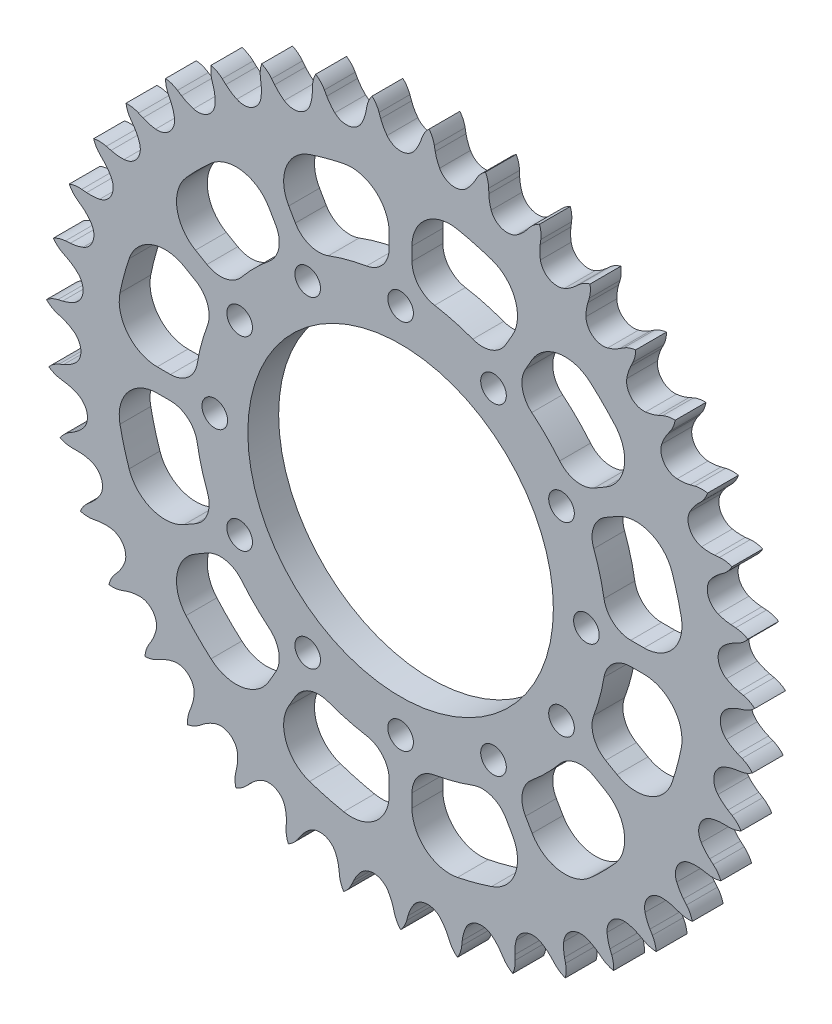
SolidWorks part; units mm, degrees
note: '?' marks a value the reader was unsure of.
material "7075-T6 (SN)"
ref_plane "Front Plane" through (0, 0, 0) normal (0, 0, 1) x (1, 0, 0)
ref_plane "Top Plane" through (0, 0, 0) normal (0, 1, 0) x (1, 0, 0)
ref_plane "Right Plane" through (0, 0, 0) normal (1, 0, 0) x (0, 0, -1)
sketch "Work Sketch" plane through (0, 0, 0) normal (0, 0, 1) x (1, 0, 0)
  line L0 (0, 0) -> (0, 160.4542) construction
  line L1 (-112.0919, 78.9148) -> (87.2579, 78.9148) construction
  line L2 (5.102, 120.8822) -> (5.102, 112.9699) construction
  line L3 (-12.8497, 82.6953) -> (16.7256, 82.6953) construction
  line L4 (5.102, 82.6953) -> (-6.0879, 74.4036) construction
  line L5 (5.102, 82.6953) -> (-4.6505, 79.1506) construction
  line L6 (-4.6505, 79.1506) -> (-6.8863, 85.3019)
  line L7 (-11.5114, 78.0206) -> (-7.1525, 78.0206) construction
  line L8 (-11.0765, 124.7602) -> (-11.0765, 110.2345) construction
  line L9 (0, 0) -> (-3.4402, 42.6146) construction
  circle A0 centre (0, 0) radius 78.9148
  circle A1 centre (0, 78.9148) radius 4.0088
  arc A2 (-4.6505, 79.1506) -> (-3.2209, 76.5281) centre (5.0804, 82.7541) ccw
  circle A3 centre (-11.0765, 78.0206) radius 6.4254
  point P23 (-3.2209, 76.5281)
  dimension "D1" = 157.8295
  dimension "D8" = 10.3767
  dimension "D2" = 8.0177
  dimension "D3" = 5.102
  dimension "D4" = 3.7806
  dimension "D5" = 36.538
  dimension "D6" = 16.564
  dimension "D7" = 10.3767
  dimension "D9" = 0.8942
  dimension "D10" = 11.0765
  dimension "D11" = 4.615
sketch "Teeth Sketch" plane through (0, 0, 0) normal (0, 0, 1) x (1, 0, 0)
  line L0 (5.0376, 80.2155) -> (4.6505, 79.1506)
  line L1 (-7.4865, 92.7372) -> (-4.7839, 59.2593) construction
  line L2 (0, 0) -> (-10.9133, 132.3061) construction
  line L3 (7.8951, 79.9848) -> (8.1063, 78.8717)
  line L4 (16093.3137, -199351.4616) -> (-16096.7539, 199394.0762) construction
  line L5 (0, 146.3285) -> (0, 56.9858) construction
  line L6 (17.8398, 78.3686) -> (17.287, 77.3797)
  line L7 (0, -200000) -> (0, 200160.4542) construction
  line L8 (20.6234, 77.6826) -> (20.6533, 76.5499)
  line L9 (-4.6505, 79.1506) -> (-6.8863, 85.3019) construction
  line L10 (44.1616, 67.154) -> (43.8313, 66.0702)
  line L11 (-5.0376, 80.2155) -> (-4.6505, 79.1506)
  line L12 (30.18, 74.4921) -> (29.4757, 73.6046)
  line L13 (32.8175, 73.3684) -> (32.6653, 72.2456)
  line L14 (41.7385, 68.6862) -> (40.901, 67.9232)
  line L15 (52.2161, 61.1014) -> (51.267, 60.4826)
  line L16 (54.362, 59.2003) -> (53.8621, 58.1836)
  line L17 (61.3413, 51.9341) -> (60.3052, 51.4756)
  line L18 (63.1544, 49.7134) -> (62.4979, 48.79)
  line L19 (68.8777, 41.4218) -> (67.7815, 41.1354)
  line L20 (70.3112, 38.939) -> (69.515, 38.1328)
  line L21 (74.6303, 29.8366) -> (73.5023, 29.7298)
  line L22 (75.6469, 27.156) -> (74.7318, 26.488)
  line L23 (78.45, 17.4787) -> (77.3195, 17.5542)
  line L24 (79.0234, 14.6698) -> (78.013, 14.1572)
  line L25 (80.2378, 4.6681) -> (79.1341, 4.9239)
  line L26 (80.3533, 1.8035) -> (79.2737, 1.4597)
  line L27 (79.9476, -8.2634) -> (78.8992, -7.8338)
  line L28 (79.602, -11.1094) -> (78.4813, -11.2756)
  line L29 (77.5867, -20.9809) -> (76.6208, -20.3887)
  line L30 (76.7891, -23.7346) -> (75.6562, -23.7189)
  line L31 (73.2164, -33.155) -> (72.358, -32.4155)
  line L32 (71.9874, -35.7451) -> (70.8717, -35.5478)
  line L33 (66.9499, -44.4704) -> (66.2212, -43.6028)
  line L34 (65.3213, -46.8298) -> (64.2517, -46.4561)
  line L35 (58.9493, -54.634) -> (58.3693, -53.6608)
  line L36 (56.9634, -56.7016) -> (55.9676, -56.1612)
  line L37 (49.422, -63.3827) -> (49.0056, -62.329)
  line L38 (47.1301, -65.1049) -> (46.2339, -64.4118)
  line L39 (38.6147, -70.4897) -> (38.3727, -69.3829)
  line L40 (36.0763, -71.822) -> (35.3028, -70.9941)
  line L41 (26.8073, -75.7712) -> (26.746, -74.6398)
  line L42 (24.088, -76.679) -> (23.4574, -75.7377)
  line L43 (14.3056, -79.0901) -> (14.4266, -77.9636)
  line L44 (11.4759, -79.55) -> (11.0044, -78.5198)
  line L45 (1.4334, -80.3607) -> (1.7335, -79.2682)
  line L46 (-1.4334, -80.3607) -> (-1.7335, -79.2682)
  line L47 (-11.4759, -79.55) -> (-11.0044, -78.5198)
  line L48 (-14.3056, -79.0901) -> (-14.4266, -77.9636)
  line L49 (-24.088, -76.679) -> (-23.4574, -75.7377)
  line L50 (-26.8073, -75.7712) -> (-26.746, -74.6398)
  line L51 (-36.0763, -71.822) -> (-35.3028, -70.9941)
  line L52 (-38.6147, -70.4897) -> (-38.3727, -69.3829)
  line L53 (-47.1301, -65.1049) -> (-46.2339, -64.4118)
  line L54 (-49.422, -63.3827) -> (-49.0056, -62.329)
  line L55 (-56.9634, -56.7016) -> (-55.9676, -56.1612)
  line L56 (-58.9493, -54.634) -> (-58.3693, -53.6608)
  line L57 (-65.3213, -46.8298) -> (-64.2517, -46.4561)
  line L58 (-66.9499, -44.4704) -> (-66.2212, -43.6028)
  line L59 (-71.9874, -35.7451) -> (-70.8717, -35.5478)
  line L60 (-73.2164, -33.155) -> (-72.358, -32.4155)
  line L61 (-76.7891, -23.7346) -> (-75.6562, -23.7189)
  line L62 (-77.5867, -20.9809) -> (-76.6208, -20.3887)
  line L63 (-79.602, -11.1094) -> (-78.4813, -11.2756)
  line L64 (-79.9476, -8.2634) -> (-78.8992, -7.8338)
  line L65 (-80.3533, 1.8035) -> (-79.2737, 1.4597)
  line L66 (-80.2378, 4.6681) -> (-79.1341, 4.9239)
  line L67 (-79.0234, 14.6698) -> (-78.013, 14.1572)
  line L68 (-78.45, 17.4787) -> (-77.3195, 17.5542)
  line L69 (-75.6469, 27.156) -> (-74.7318, 26.488)
  line L70 (-74.6303, 29.8366) -> (-73.5023, 29.7298)
  line L71 (-70.3112, 38.939) -> (-69.515, 38.1328)
  line L72 (-68.8777, 41.4218) -> (-67.7815, 41.1354)
  line L73 (-63.1544, 49.7134) -> (-62.4979, 48.79)
  line L74 (-61.3413, 51.9341) -> (-60.3052, 51.4756)
  line L75 (-54.362, 59.2003) -> (-53.8621, 58.1836)
  line L76 (-52.2161, 61.1014) -> (-51.267, 60.4826)
  line L77 (-44.1616, 67.154) -> (-43.8313, 66.0702)
  line L78 (-41.7385, 68.6862) -> (-40.901, 67.9232)
  line L79 (-32.8175, 73.3684) -> (-32.6653, 72.2456)
  line L80 (-30.18, 74.4921) -> (-29.4757, 73.6046)
  line L81 (-20.6234, 77.6826) -> (-20.6533, 76.5499)
  line L82 (-17.8398, 78.3686) -> (-17.287, 77.3797)
  line L83 (-7.8951, 79.9848) -> (-8.1063, 78.8717)
  arc A0 (-6.8336, 82.8459) -> (-5.0376, 80.2155) centre (-11.0765, 78.0206) cw
  circle A1 centre (-11.0765, 78.0206) radius 6.4254 construction
  arc A2 (-3.1753, 76.4677) -> (-4.6505, 79.1506) centre (5.0804, 82.7541) cw
  arc A3 (-4.6505, 79.1506) -> (-3.2209, 76.5281) centre (5.0804, 82.7541) ccw construction
  circle A4 centre (0, 78.9148) radius 4.0088 construction
  arc A5 (-3.1753, 76.4677) -> (3.1753, 76.4677) centre (0, 78.9148) ccw
  arc A6 (3.1753, 76.4677) -> (4.6505, 79.1506) centre (-5.0804, 82.7541) ccw
  arc A7 (6.8336, 82.8459) -> (5.0376, 80.2155) centre (11.0765, 78.0206) ccw
  arc A8 (6.5443, 82.8692) -> (7.8951, 79.9848) centre (1.5824, 78.787) cw
  arc A9 (9.1321, 75.9868) -> (8.1063, 78.8717) centre (18.2893, 80.8676) cw
  arc A10 (9.1321, 75.9868) -> (15.4004, 74.9681) centre (12.6588, 77.8928) ccw
  arc A11 (15.4004, 74.9681) -> (17.287, 77.3797) centre (8.2601, 82.4975) ccw
  arc A12 (20.0345, 80.6769) -> (17.8398, 78.3686) centre (23.4484, 75.2334) ccw
  arc A13 (19.7528, 80.7463) -> (20.6234, 77.6826) centre (14.2002, 77.5129) cw
  arc A14 (21.203, 73.5379) -> (20.6533, 76.5499) centre (31.0245, 76.8865) cw
  arc A15 (21.203, 73.5379) -> (27.2267, 71.5268) centre (24.9898, 74.8535) ccw
  arc A16 (27.2267, 71.5268) -> (29.4757, 73.6046) centre (21.3867, 80.1041) ccw
  arc A17 (32.7165, 76.4184) -> (30.18, 74.4921) centre (35.2131, 70.4978) ccw
  arc A18 (32.4496, 76.5321) -> (32.8175, 73.3684) centre (26.4502, 74.2313) cw
  arc A19 (32.7247, 69.1844) -> (32.6653, 72.2456) centre (42.9562, 70.9142) cw
  arc A20 (32.7247, 69.1844) -> (38.3479, 66.2331) centre (36.6735, 69.8756) ccw
  arc A21 (38.3479, 66.2331) -> (40.901, 67.9232) centre (33.9593, 75.6361) ccw
  arc A22 (44.5512, 70.1807) -> (41.7385, 68.6862) centre (46.0657, 63.9363) ccw
  arc A23 (44.306, 70.3358) -> (44.1616, 67.154) centre (38.0153, 69.0271) cw
  arc A24 (43.3989, 63.039) -> (43.8313, 66.0702) centre (53.7754, 63.1052) cw
  arc A25 (43.3989, 63.039) -> (48.4758, 59.224) centre (47.4074, 63.0878) ccw
  arc A26 (48.4758, 59.224) -> (51.267, 60.4826) centre (45.6524, 69.2092) ccw
  arc A27 (55.2321, 62.1253) -> (52.2161, 61.1014) centre (55.7253, 55.7189) ccw
  arc A28 (55.0149, 62.3178) -> (54.362, 59.2003) centre (48.5957, 62.0351) cw
  arc A29 (52.9491, 55.261) -> (53.8621, 58.1836) centre (63.2018, 53.6618) cw
  arc A30 (52.9491, 55.261) -> (57.3483, 50.681) centre (56.9135, 54.6662) ccw
  arc A31 (57.3483, 50.681) -> (60.3052, 51.4756) centre (56.1632, 60.9898) ccw
  arc A32 (64.4824, 52.461) -> (61.3413, 51.9341) centre (63.9416, 46.0584) ccw
  arc A33 (64.2989, 52.6858) -> (63.1544, 49.7134) centre (57.9175, 53.4365) cw
  arc A34 (61.1279, 46.0518) -> (62.4979, 48.79) centre (70.9913, 42.8287) cw
  arc A35 (61.1279, 46.0518) -> (64.7354, 40.8254) centre (64.9456, 44.8287) ccw
  arc A36 (64.7354, 40.8254) -> (67.7815, 41.1354) centre (65.2193, 51.1908) ccw
  arc A37 (72.0627, 41.4379) -> (68.8777, 41.4218) centre (70.5018, 35.205) ccw
  arc A38 (71.9177, 41.6892) -> (70.3112, 38.939) centre (65.7393, 43.4539) cw
  arc A39 (67.7235, 35.6498) -> (69.515, 38.1328) centre (76.9422, 30.8862) cw
  arc A40 (67.7235, 35.6498) -> (70.446, 29.9124) centre (71.2956, 33.8302) ccw
  arc A41 (70.446, 29.9124) -> (73.5023, 29.7298) centre (72.5864, 40.0659) ccw
  arc A42 (77.7767, 29.3416) -> (74.6303, 29.8366) centre (75.2361, 23.4398) ccw
  arc A43 (77.6738, 29.6129) -> (75.6469, 27.156) centre (71.8585, 32.3458) cw
  arc A44 (72.5652, 24.3246) -> (74.7318, 26.488) centre (80.9003, 18.1439) cw
  arc A45 (72.5652, 24.3246) -> (74.332, 18.2247) centre (75.7991, 21.9555) ccw
  arc A46 (74.332, 18.2247) -> (77.3195, 17.5542) centre (78.0734, 27.9034) ccw
  arc A47 (81.4762, 16.4854) -> (78.45, 17.4787) centre (78.0218, 11.0675) ccw
  arc A48 (81.4182, 16.7697) -> (79.0234, 14.6698) centre (76.1166, 20.4) cw
  arc A49 (75.5274, 12.3693) -> (78.013, 14.1572) centre (82.7631, 4.9316) cw
  arc A50 (75.5274, 12.3693) -> (76.2929, 6.065) centre (78.3394, 9.5121) ccw
  arc A51 (76.2929, 6.065) -> (79.1341, 4.9239) centre (81.5384, 15.0182) ccw
  arc A52 (83.0656, 3.2022) -> (80.2378, 4.6681) centre (78.7868, -1.5914) ccw
  arc A53 (83.0539, 3.4922) -> (80.3533, 1.8035) centre (78.4033, 7.9259) cw
  arc A54 (76.5335, 0.0937) -> (79.2737, 1.4597) centre (82.4825, -8.4084) cw
  arc A55 (76.5335, 0.0937) -> (76.2778, -6.2518) centre (78.8508, -3.1776) ccw
  arc A56 (76.2778, -6.2518) -> (78.8992, -7.8338) centre (82.8916, 1.7441) ccw
  arc A57 (82.5035, -10.1639) -> (79.9476, -8.2634) centre (77.5113, -14.2091) ccw
  arc A58 (82.5385, -9.8758) -> (79.602, -11.1094) centre (78.6594, -4.7535) cw
  arc A59 (75.5574, -12.1844) -> (78.4813, -11.2756) centre (80.0655, -21.5307) cw
  arc A60 (75.5574, -12.1844) -> (74.2872, -18.4066) centre (77.3199, -15.785) ccw
  arc A61 (74.2872, -18.4066) -> (76.6208, -20.3887) centre (82.0979, -11.5753) ccw
  arc A62 (79.8047, -23.2668) -> (77.5867, -20.9809) centre (74.2283, -26.4587) ccw
  arc A63 (79.8855, -22.9881) -> (76.7891, -23.7346) centre (76.8783, -17.3098) cw
  arc A64 (72.6245, -24.1469) -> (75.6562, -23.7189) centre (75.5749, -34.0953) cw
  arc A65 (72.6245, -24.1469) -> (70.3725, -30.0848) centre (73.7866, -27.9836) ccw
  arc A66 (70.3725, -30.0848) -> (72.358, -32.4155) centre (79.178, -24.5948) ccw
  arc A67 (75.039, -35.7671) -> (73.2164, -33.155) centre (69.0227, -38.0232) ccw
  arc A68 (75.1634, -35.5049) -> (71.9874, -35.7451) centre (73.106, -29.4178) cw
  arc A69 (67.8106, -35.484) -> (70.8717, -35.5478) centre (69.127, -45.7768) cw
  arc A70 (67.8106, -35.484) -> (64.6353, -40.9837) centre (68.3422, -39.4574) ccw
  arc A71 (64.6353, -40.9837) -> (66.2212, -43.6028) centre (74.2074, -36.9773) ccw
  arc A72 (68.3299, -47.341) -> (66.9499, -44.4704) centre (62.0296, -48.6028) ccw
  arc A73 (68.4947, -47.1022) -> (65.3213, -46.8298) centre (67.4404, -40.7639) cw
  arc A74 (61.2404, -45.902) -> (64.2517, -46.4561) centre (60.8887, -56.2728) cw
  arc A75 (61.2404, -45.902) -> (57.224, -50.8212) centre (61.1278, -49.9093) ccw
  arc A76 (57.224, -50.8212) -> (58.3693, -53.6608) centre (67.3148, -48.4022) ccw
  arc A77 (59.851, -57.6888) -> (58.9493, -54.634) centre (53.4299, -57.9236) ccw
  arc A78 (60.052, -57.4796) -> (56.9634, -56.7016) centre (60.0281, -51.0542) cw
  arc A79 (53.0842, -55.1313) -> (55.9676, -56.1612) centre (51.0734, -65.3113) cw
  arc A80 (53.0842, -55.1313) -> (48.3307, -59.3425) centre (52.3302, -59.0685) ccw
  arc A81 (48.3307, -59.3425) -> (49.0056, -62.329) centre (58.6789, -58.5735) ccw
  arc A82 (49.822, -66.5425) -> (49.422, -63.3827) centre (43.4464, -65.7443) ccw
  arc A83 (50.054, -66.3682) -> (47.1301, -65.1049) centre (51.0611, -60.0222) cw
  arc A84 (43.5531, -62.9326) -> (46.2339, -64.4118) centre (39.9354, -72.6583) cw
  arc A85 (43.5531, -62.9326) -> (38.1856, -66.3268) centre (42.1772, -66.698) ccw
  arc A86 (38.1856, -66.3268) -> (38.3727, -69.3829) centre (48.5231, -67.2277) ccw
  arc A87 (38.5026, -73.6728) -> (38.6147, -70.4897) centre (32.3376, -71.8622) ccw
  arc A88 (38.7596, -73.538) -> (36.0763, -71.822) centre (40.7716, -67.4357) cw
  arc A89 (32.894, -69.1041) -> (35.3028, -70.9941) centre (27.763, -78.1234) cw
  arc A90 (32.894, -69.1041) -> (27.0516, -71.5933) centre (30.932, -72.6) ccw
  arc A91 (27.0516, -71.5933) -> (26.746, -74.6398) centre (37.1107, -74.1408) ccw
  arc A92 (26.1861, -78.8951) -> (26.8073, -75.7712) centre (20.3913, -76.1189) ccw
  arc A93 (26.4613, -78.8032) -> (24.088, -76.679) centre (29.4261, -73.1027) cw
  arc A94 (21.3829, -73.4858) -> (23.4574, -75.7377) centre (14.8716, -81.5653) cw
  arc A95 (21.3829, -73.4858) -> (15.2169, -75.0055) centre (18.8855, -76.6216) ccw
  arc A96 (15.2169, -75.0055) -> (14.4266, -77.9636) centre (24.7371, -79.1336) ccw
  arc A97 (13.1913, -82.0739) -> (14.3056, -79.0901) centre (7.9169, -78.4042) ccw
  arc A98 (13.4777, -82.0274) -> (11.4759, -79.55) centre (17.3186, -76.8763) cw
  arc A99 (9.3181, -75.9642) -> (11.0044, -78.5198) centre (1.595, -82.8946) cw
  arc A100 (9.3181, -75.9642) -> (2.9881, -76.4752) centre (6.35, -78.6589) ccw
  arc A101 (2.9881, -76.4752) -> (1.7335, -79.2682) centre (11.7228, -82.077) ccw
  arc A102 (-0.1451, -83.1271) -> (1.4334, -80.3607) centre (-4.7625, -78.6589) ccw
  arc A103 (0.1451, -83.1271) -> (-1.4334, -80.3607) centre (4.7625, -78.6589) cw
  arc A104 (-2.9881, -76.4752) -> (-1.7335, -79.2682) centre (-11.7228, -82.077) cw
  arc A105 (-2.9881, -76.4752) -> (-9.3181, -75.9642) centre (-6.35, -78.6589) ccw
  arc A106 (-9.3181, -75.9642) -> (-11.0044, -78.5198) centre (-1.595, -82.8946) ccw
  arc A107 (-13.4777, -82.0274) -> (-11.4759, -79.55) centre (-17.3186, -76.8763) ccw
  arc A108 (-13.1913, -82.0739) -> (-14.3056, -79.0901) centre (-7.9169, -78.4042) cw
  arc A109 (-15.2169, -75.0055) -> (-14.4266, -77.9636) centre (-24.7371, -79.1336) cw
  arc A110 (-15.2169, -75.0055) -> (-21.3829, -73.4858) centre (-18.8855, -76.6216) ccw
  arc A111 (-21.3829, -73.4858) -> (-23.4574, -75.7377) centre (-14.8716, -81.5653) ccw
  arc A112 (-26.4613, -78.8032) -> (-24.088, -76.679) centre (-29.4261, -73.1027) ccw
  arc A113 (-26.1861, -78.8951) -> (-26.8073, -75.7712) centre (-20.3913, -76.1189) cw
  arc A114 (-27.0516, -71.5933) -> (-26.746, -74.6398) centre (-37.1107, -74.1408) cw
  arc A115 (-27.0516, -71.5933) -> (-32.894, -69.1041) centre (-30.932, -72.6) ccw
  arc A116 (-32.894, -69.1041) -> (-35.3028, -70.9941) centre (-27.763, -78.1234) ccw
  arc A117 (-38.7596, -73.538) -> (-36.0763, -71.822) centre (-40.7716, -67.4357) ccw
  arc A118 (-38.5026, -73.6728) -> (-38.6147, -70.4897) centre (-32.3376, -71.8622) cw
  arc A119 (-38.1856, -66.3268) -> (-38.3727, -69.3829) centre (-48.5231, -67.2277) cw
  arc A120 (-38.1856, -66.3268) -> (-43.5531, -62.9326) centre (-42.1772, -66.698) ccw
  arc A121 (-43.5531, -62.9326) -> (-46.2339, -64.4118) centre (-39.9354, -72.6583) ccw
  arc A122 (-50.054, -66.3682) -> (-47.1301, -65.1049) centre (-51.0611, -60.0222) ccw
  arc A123 (-49.822, -66.5425) -> (-49.422, -63.3827) centre (-43.4464, -65.7443) cw
  arc A124 (-48.3307, -59.3425) -> (-49.0056, -62.329) centre (-58.6789, -58.5735) cw
  arc A125 (-48.3307, -59.3425) -> (-53.0842, -55.1313) centre (-52.3302, -59.0685) ccw
  arc A126 (-53.0842, -55.1313) -> (-55.9676, -56.1612) centre (-51.0734, -65.3113) ccw
  arc A127 (-60.052, -57.4796) -> (-56.9634, -56.7016) centre (-60.0281, -51.0542) ccw
  arc A128 (-59.851, -57.6888) -> (-58.9493, -54.634) centre (-53.4299, -57.9236) cw
  arc A129 (-57.224, -50.8212) -> (-58.3693, -53.6608) centre (-67.3148, -48.4022) cw
  arc A130 (-57.224, -50.8212) -> (-61.2404, -45.902) centre (-61.1278, -49.9093) ccw
  arc A131 (-61.2404, -45.902) -> (-64.2517, -46.4561) centre (-60.8887, -56.2728) ccw
  arc A132 (-68.4947, -47.1022) -> (-65.3213, -46.8298) centre (-67.4404, -40.7639) ccw
  arc A133 (-68.3299, -47.341) -> (-66.9499, -44.4704) centre (-62.0296, -48.6028) cw
  arc A134 (-64.6353, -40.9837) -> (-66.2212, -43.6028) centre (-74.2074, -36.9773) cw
  arc A135 (-64.6353, -40.9837) -> (-67.8106, -35.484) centre (-68.3422, -39.4574) ccw
  arc A136 (-67.8106, -35.484) -> (-70.8717, -35.5478) centre (-69.127, -45.7768) ccw
  arc A137 (-75.1634, -35.5049) -> (-71.9874, -35.7451) centre (-73.106, -29.4178) ccw
  arc A138 (-75.039, -35.7671) -> (-73.2164, -33.155) centre (-69.0227, -38.0232) cw
  arc A139 (-70.3725, -30.0848) -> (-72.358, -32.4155) centre (-79.178, -24.5948) cw
  arc A140 (-70.3725, -30.0848) -> (-72.6245, -24.1469) centre (-73.7866, -27.9836) ccw
  arc A141 (-72.6245, -24.1469) -> (-75.6562, -23.7189) centre (-75.5749, -34.0953) ccw
  arc A142 (-79.8855, -22.9881) -> (-76.7891, -23.7346) centre (-76.8783, -17.3098) ccw
  arc A143 (-79.8047, -23.2668) -> (-77.5867, -20.9809) centre (-74.2283, -26.4587) cw
  arc A144 (-74.2872, -18.4066) -> (-76.6208, -20.3887) centre (-82.0979, -11.5753) cw
  arc A145 (-74.2872, -18.4066) -> (-75.5574, -12.1844) centre (-77.3199, -15.785) ccw
  arc A146 (-75.5574, -12.1844) -> (-78.4813, -11.2756) centre (-80.0655, -21.5307) ccw
  arc A147 (-82.5385, -9.8758) -> (-79.602, -11.1094) centre (-78.6594, -4.7535) ccw
  arc A148 (-82.5035, -10.1639) -> (-79.9476, -8.2634) centre (-77.5113, -14.2091) cw
  arc A149 (-76.2778, -6.2518) -> (-78.8992, -7.8338) centre (-82.8916, 1.7441) cw
  arc A150 (-76.2778, -6.2518) -> (-76.5335, 0.0937) centre (-78.8508, -3.1776) ccw
  arc A151 (-76.5335, 0.0937) -> (-79.2737, 1.4597) centre (-82.4825, -8.4084) ccw
  arc A152 (-83.0539, 3.4922) -> (-80.3533, 1.8035) centre (-78.4033, 7.9259) ccw
  arc A153 (-83.0656, 3.2022) -> (-80.2378, 4.6681) centre (-78.7868, -1.5914) cw
  arc A154 (-76.2929, 6.065) -> (-79.1341, 4.9239) centre (-81.5384, 15.0182) cw
  arc A155 (-76.2929, 6.065) -> (-75.5274, 12.3693) centre (-78.3394, 9.5121) ccw
  arc A156 (-75.5274, 12.3693) -> (-78.013, 14.1572) centre (-82.7631, 4.9316) ccw
  arc A157 (-81.4182, 16.7697) -> (-79.0234, 14.6698) centre (-76.1166, 20.4) ccw
  arc A158 (-81.4762, 16.4854) -> (-78.45, 17.4787) centre (-78.0218, 11.0675) cw
  arc A159 (-74.332, 18.2247) -> (-77.3195, 17.5542) centre (-78.0734, 27.9034) cw
  arc A160 (-74.332, 18.2247) -> (-72.5652, 24.3246) centre (-75.7991, 21.9555) ccw
  arc A161 (-72.5652, 24.3246) -> (-74.7318, 26.488) centre (-80.9003, 18.1439) ccw
  arc A162 (-77.6738, 29.6129) -> (-75.6469, 27.156) centre (-71.8585, 32.3458) ccw
  arc A163 (-77.7767, 29.3416) -> (-74.6303, 29.8366) centre (-75.2361, 23.4398) cw
  arc A164 (-70.446, 29.9124) -> (-73.5023, 29.7298) centre (-72.5864, 40.0659) cw
  arc A165 (-70.446, 29.9124) -> (-67.7235, 35.6498) centre (-71.2956, 33.8302) ccw
  arc A166 (-67.7235, 35.6498) -> (-69.515, 38.1328) centre (-76.9422, 30.8862) ccw
  arc A167 (-71.9177, 41.6892) -> (-70.3112, 38.939) centre (-65.7393, 43.4539) ccw
  arc A168 (-72.0627, 41.4379) -> (-68.8777, 41.4218) centre (-70.5018, 35.205) cw
  arc A169 (-64.7354, 40.8254) -> (-67.7815, 41.1354) centre (-65.2193, 51.1908) cw
  arc A170 (-64.7354, 40.8254) -> (-61.1279, 46.0518) centre (-64.9456, 44.8287) ccw
  arc A171 (-61.1279, 46.0518) -> (-62.4979, 48.79) centre (-70.9913, 42.8287) ccw
  arc A172 (-64.2989, 52.6858) -> (-63.1544, 49.7134) centre (-57.9175, 53.4365) ccw
  arc A173 (-64.4824, 52.461) -> (-61.3413, 51.9341) centre (-63.9416, 46.0584) cw
  arc A174 (-57.3483, 50.681) -> (-60.3052, 51.4756) centre (-56.1632, 60.9898) cw
  arc A175 (-57.3483, 50.681) -> (-52.9491, 55.261) centre (-56.9135, 54.6662) ccw
  arc A176 (-52.9491, 55.261) -> (-53.8621, 58.1836) centre (-63.2018, 53.6618) ccw
  arc A177 (-55.0149, 62.3178) -> (-54.362, 59.2003) centre (-48.5957, 62.0351) ccw
  arc A178 (-55.2321, 62.1253) -> (-52.2161, 61.1014) centre (-55.7253, 55.7189) cw
  arc A179 (-48.4758, 59.224) -> (-51.267, 60.4826) centre (-45.6524, 69.2092) cw
  arc A180 (-48.4758, 59.224) -> (-43.3989, 63.039) centre (-47.4074, 63.0878) ccw
  arc A181 (-43.3989, 63.039) -> (-43.8313, 66.0702) centre (-53.7754, 63.1052) ccw
  arc A182 (-44.306, 70.3358) -> (-44.1616, 67.154) centre (-38.0153, 69.0271) ccw
  arc A183 (-44.5512, 70.1807) -> (-41.7385, 68.6862) centre (-46.0657, 63.9363) cw
  arc A184 (-38.3479, 66.2331) -> (-40.901, 67.9232) centre (-33.9593, 75.6361) cw
  arc A185 (-38.3479, 66.2331) -> (-32.7247, 69.1844) centre (-36.6735, 69.8756) ccw
  arc A186 (-32.7247, 69.1844) -> (-32.6653, 72.2456) centre (-42.9562, 70.9142) ccw
  arc A187 (-32.4496, 76.5321) -> (-32.8175, 73.3684) centre (-26.4502, 74.2313) ccw
  arc A188 (-32.7165, 76.4184) -> (-30.18, 74.4921) centre (-35.2131, 70.4978) cw
  arc A189 (-27.2267, 71.5268) -> (-29.4757, 73.6046) centre (-21.3867, 80.1041) cw
  arc A190 (-27.2267, 71.5268) -> (-21.203, 73.5379) centre (-24.9898, 74.8535) ccw
  arc A191 (-21.203, 73.5379) -> (-20.6533, 76.5499) centre (-31.0245, 76.8865) ccw
  arc A192 (-19.7528, 80.7463) -> (-20.6234, 77.6826) centre (-14.2002, 77.5129) ccw
  arc A193 (-20.0345, 80.6769) -> (-17.8398, 78.3686) centre (-23.4484, 75.2334) cw
  arc A194 (-15.4004, 74.9681) -> (-17.287, 77.3797) centre (-8.2601, 82.4975) cw
  arc A195 (-15.4004, 74.9681) -> (-9.1321, 75.9868) centre (-12.6588, 77.8928) ccw
  arc A196 (-9.1321, 75.9868) -> (-8.1063, 78.8717) centre (-18.2893, 80.8676) ccw
  arc A197 (-6.5443, 82.8692) -> (-7.8951, 79.9848) centre (-1.5824, 78.787) ccw
  point P77 (0, 0)
  dimension "D1" = 4.615
  dimension "D2" = 4.715
  dimension "D3" = 39
extrude "Extrusion" add sketch "Teeth Sketch" along normal blind 7.2136
sketch "Sketch1" plane through (0, 0, 0) normal (0, 0, -1) x (-1, 0, 0)
  circle A0 centre (0, 0) radius 78.9443
  circle A1 centre (0, 0) radius 35.7643
  dimension "D1" = 43.18
extrude "Cut-Extrude" cut sketch "Sketch1" against normal through all both and the other way through all contours A1
ref_axis "Axis1" [suppressed] through (0, 0, 7.2136) along (0, 0, -1)?
ref_plane "Sprocket Center Plane" through (0, 0, 3.6068) normal (0, 0, 1) x (1, 0, 0)
sketch "Pitch Circle" plane through (0, 0, 3.6068) normal (0, 0, -1) x (-1, 0, 0)
  circle A0 centre (0, 0) radius 82.9531 construction
  dimension "D1" = 165.9063
sketch "Chain Pitch Circle" plane through (0, 0, 0) normal (0, 0, -1) x (-1, 0, 0)
  circle A0 centre (0, 0) radius 82.9531 construction
  dimension "D1" = 165.9063
ref_plane "Center Plane" through (0, 0, 3.6068) normal (0, 0, 1) x (1, 0, 0)
hole_wizard "Ø6.0mm Dowel Hole1" positions "Sketch7" profile "Sketch8" hole size "Ø6.0" standard "ANSI Metric" end condition through all
sketch "Sketch7" plane through (0, 0, 7.2136) normal (0, 0, 1) x (1, 0, 0)
  point P0 (-43.5, 0)
  dimension "D1" = 43.5
sketch "Sketch8" plane through (-43.5, 0, 7.2136) normal (1, 0, 0) x (0, -1, 0)
  line L0 (0, 0) -> (0, 7.2136)
  line L1 (0, 7.2136) -> (3, 7.2136)
  line L2 (3, 7.2136) -> (3, 0)
  line L5 (3, 0) -> (0, 0)
  line L11 (0, -6.35) -> (0, 107.95) construction
  dimension "Thru Hole Dia." = 6
  dimension "Thru Hole Depth" = 7.2136
pattern_circular "CirPattern1" count 12 over 360 about axis through (0, 0, 0) along (0, 0, 1) of "Ø6.0mm Dowel Hole1"
sketch "Sketch9" plane through (0, 0, 7.2136) normal (0, 0, 1) x (1, 0, 0)
  line L0 (0, 0) -> (0, 74.9059)
  line L1 (-2.667, 48.2043) -> (-2.667, 66.9788)
  line L2 (2.667, 48.2043) -> (2.667, 66.9788)
  line L3 (26.4118, 40.4126) -> (35.7991, 56.6719)
  line L4 (21.7924, 43.0796) -> (31.1797, 59.3389)
  line L5 (43.0796, 21.7924) -> (59.3389, 31.1797)
  line L6 (40.4126, 26.4118) -> (56.6719, 35.7991)
  line L7 (48.2043, -2.667) -> (66.9788, -2.667)
  line L8 (48.2043, 2.667) -> (66.9788, 2.667)
  line L9 (40.4126, -26.4118) -> (56.6719, -35.7991)
  line L10 (43.0796, -21.7924) -> (59.3389, -31.1797)
  line L11 (21.7924, -43.0796) -> (31.1797, -59.3389)
  line L12 (26.4118, -40.4126) -> (35.7991, -56.6719)
  line L13 (-2.667, -48.2043) -> (-2.667, -66.9788)
  line L14 (2.667, -48.2043) -> (2.667, -66.9788)
  line L15 (-26.4118, -40.4126) -> (-35.7991, -56.6719)
  line L16 (-21.7924, -43.0796) -> (-31.1797, -59.3389)
  line L17 (-43.0796, -21.7924) -> (-59.3389, -31.1797)
  line L18 (-40.4126, -26.4118) -> (-56.6719, -35.7991)
  line L19 (-48.2043, 2.667) -> (-66.9788, 2.667)
  line L20 (-48.2043, -2.667) -> (-66.9788, -2.667)
  line L21 (-40.4126, 26.4118) -> (-56.6719, 35.7991)
  line L30 (-43.0796, 21.7924) -> (-59.3389, 31.1797)
  line L31 (-21.7924, 43.0796) -> (-31.1797, 59.3389)
  line L32 (-26.4118, 40.4126) -> (-35.7991, 56.6719)
  circle A0 centre (0, 0) radius 74.9059
  circle A1 centre (0, 0) radius 46.5
  circle A2 centre (0, 0) radius 40.5
  circle A4 centre (0, 0) radius 48.278
  circle A6 centre (0, 0) radius 67.0319
  point P8 (3.175, 0)
  point P11 (3.175, 67.2859)
  point P12 (-3.175, 0)
  point P13 (-3.175, 67.2802)
  point P55 (0.0303, 0.0361)
  point P83 (0, 0)
  dimension "D2" = 7.874
  dimension "D3" = 5.334
  dimension "D1" = 1.778
  dimension "D4" = 12
extrude "Cut-Out1" cut sketch "Sketch9" against normal through all contours L1 A6 L31 A4 | L4 A6 L2 A4 | L32 A6 L21 A4 | L30 A6 L19 A4 | L20 A6 L17 A4 | L18 A6 L15 A4 | L16 A6 L13 A4 | L14 A6 L11 A4 | L12 A6 L9 A4 | L10 A6 L7 A4 | L8 A6 L5 A4 | L6 A6 L3 A4
sketch "Sketch11" plane through (0, 0, 7.2136) normal (0, 0, 1) x (1, 0, 0)
  line L0 (2.667, 48.2043) -> (2.667, 66.9788) construction
  line L1 (-2.667, 48.2043) -> (-2.667, 66.9788) construction
  line L2 (0, 0) -> (0, 74.9059) construction
  line L3 (48.2043, 2.667) -> (66.9788, 2.667) construction
  line L4 (48.2043, -2.667) -> (66.9788, -2.667) construction
  line L5 (40.4126, 26.4118) -> (56.6719, 35.7991) construction
  line L6 (43.0796, 21.7924) -> (59.3389, 31.1797) construction
  line L7 (21.7924, 43.0796) -> (31.1797, 59.3389) construction
  line L8 (26.4118, 40.4126) -> (35.7991, 56.6719) construction
  line L9 (-21.7924, -43.0796) -> (-31.1797, -59.3389) construction
  line L10 (-26.4118, -40.4126) -> (-35.7991, -56.6719) construction
  line L11 (2.667, -48.2043) -> (2.667, -66.9788) construction
  line L12 (-2.667, -48.2043) -> (-2.667, -66.9788) construction
  line L13 (26.4118, -40.4126) -> (35.7991, -56.6719) construction
  line L14 (21.7924, -43.0796) -> (31.1797, -59.3389) construction
  line L15 (43.0796, -21.7924) -> (59.3389, -31.1797) construction
  line L16 (40.4126, -26.4118) -> (56.6719, -35.7991) construction
  line L17 (-48.2043, -2.667) -> (-66.9788, -2.667) construction
  line L18 (-48.2043, 2.667) -> (-66.9788, 2.667) construction
  line L19 (-40.4126, -26.4118) -> (-56.6719, -35.7991) construction
  line L20 (-43.0796, -21.7924) -> (-59.3389, -31.1797) construction
  line L21 (-26.4118, 40.4126) -> (-35.7991, 56.6719) construction
  line L22 (-43.0796, 21.7924) -> (-59.3389, 31.1797) construction
  line L23 (-40.4126, 26.4118) -> (-56.6719, 35.7991) construction
  line L24 (-21.7924, 43.0796) -> (-31.1797, 59.3389) construction
  line L25 (2.667, 48.2043) -> (2.667, 66.9788)
  line L26 (-2.667, 48.2043) -> (-2.667, 66.9788)
  line L27 (0, 0) -> (0, 74.9059)
  line L28 (48.2043, 2.667) -> (66.9788, 2.667)
  line L29 (48.2043, -2.667) -> (66.9788, -2.667)
  line L30 (40.4126, 26.4118) -> (56.6719, 35.7991)
  line L31 (43.0796, 21.7924) -> (59.3389, 31.1797)
  line L32 (21.7924, 43.0796) -> (31.1797, 59.3389)
  line L33 (26.4118, 40.4126) -> (35.7991, 56.6719)
  line L34 (-21.7924, -43.0796) -> (-31.1797, -59.3389)
  line L35 (-26.4118, -40.4126) -> (-35.7991, -56.6719)
  line L36 (2.667, -48.2043) -> (2.667, -66.9788)
  line L37 (-2.667, -48.2043) -> (-2.667, -66.9788)
  line L38 (26.4118, -40.4126) -> (35.7991, -56.6719)
  line L39 (21.7924, -43.0796) -> (31.1797, -59.3389)
  line L40 (43.0796, -21.7924) -> (59.3389, -31.1797)
  line L41 (40.4126, -26.4118) -> (56.6719, -35.7991)
  line L42 (-48.2043, -2.667) -> (-66.9788, -2.667)
  line L43 (-48.2043, 2.667) -> (-66.9788, 2.667)
  line L44 (-40.4126, -26.4118) -> (-56.6719, -35.7991)
  line L45 (-43.0796, -21.7924) -> (-59.3389, -31.1797)
  line L46 (-26.4118, 40.4126) -> (-35.7991, 56.6719)
  line L47 (-43.0796, 21.7924) -> (-59.3389, 31.1797)
  line L48 (-40.4126, 26.4118) -> (-56.6719, 35.7991)
  line L49 (-21.7924, 43.0796) -> (-31.1797, 59.3389)
  line L50 (0, 43.5) -> (21.75, 37.6721)
  line L51 (7.4721, 41.4979) -> (5.8086, 35.2894)
  line L52 (14.2779, 39.6743) -> (12.6143, 33.4658)
  circle A0 centre (0, 43.5) radius 7.7357
  circle A1 centre (0, 0) radius 40.5
  circle A2 centre (0, 0) radius 40.5
  circle A3 centre (0, 0) radius 46.5
  circle A4 centre (0, 0) radius 46.5
  circle A5 centre (0, 0) radius 74.9059
  circle A6 centre (0, 0) radius 74.9059
  circle A7 centre (0, 0) radius 67.0319
  circle A8 centre (0, 0) radius 67.0319
  circle A9 centre (0, 0) radius 48.278
  circle A10 centre (0, 0) radius 48.278
  circle A11 centre (21.75, 37.6721) radius 7.7357
  circle A12 centre (0, 0) radius 35.7643 construction
  circle A13 centre (0, 0) radius 35.7643
  dimension "D1" = 0
  dimension "D2" = 0
  dimension "D3" = 0
  dimension "D4" = 0
  dimension "D5" = 0
extrude "Cut -Out2" [suppressed] cut sketch "Sketch11" against normal through all contours A13 A11 A2 A0 | A11 A4 A0 A2 | A11 A10 A0 A4 | A2 L52 L50 L51 | A13 A11 A2 L52 | A13 L51 A2 A0 | A2 L51 A0 | A11 L52 A2
pattern_circular "CirPattern22" [suppressed] count 12 over 360
fillet "Fillet2" radius 6.35 24 edges at (-40.4126, 26.4118, 3.6068) (-26.4118, 40.4126, 3.6068) (-2.667, 48.2043, 3.6068) (-21.7924, 43.0796, 3.6068) (-43.0796, 21.7924, 3.6068) (-48.2043, 2.667, 3.6068) (-48.2043, -2.667, 3.6068) (-43.0796, -21.7924, 3.6068) (-40.4126, -26.4118, 3.6068) (-26.4118, -40.4126, 3.6068) (-21.7924, -43.0796, 3.6068) (-2.667, -48.2043, 3.6068) (2.667, -48.2043, 3.6068) (21.7924, -43.0796, 3.6068) (26.4118, -40.4126, 3.6068) (40.4126, -26.4118, 3.6068) (43.0796, -21.7924, 3.6068) (48.2043, -2.667, 3.6068) (48.2043, 2.667, 3.6068) (43.0796, 21.7924, 3.6068) (40.4126, 26.4118, 3.6068) (26.4118, 40.4126, 3.6068) (2.667, 48.2043, 3.6068) (21.7924, 43.0796, 3.6068)
fillet "Fillet3" radius 8.89 24 edges at (-59.3389, 31.1797, 3.6068) (-66.9788, 2.667, 3.6068) (-66.9788, -2.667, 3.6068) (-59.3389, -31.1797, 3.6068) (-56.6719, -35.7991, 3.6068) (-35.7991, -56.6719, 3.6068) (-31.1797, -59.3389, 3.6068) (-2.667, -66.9788, 3.6068) (31.1797, -59.3389, 3.6068) (2.667, -66.9788, 3.6068) (56.6719, -35.7991, 3.6068) (35.7991, -56.6719, 3.6068) (59.3389, -31.1797, 3.6068) (66.9788, -2.667, 3.6068) (66.9788, 2.667, 3.6068) (59.3389, 31.1797, 3.6068) (56.6719, 35.7991, 3.6068) (35.7991, 56.6719, 3.6068) (31.1797, 59.3389, 3.6068) (2.667, 66.9788, 3.6068) (-2.667, 66.9788, 3.6068) (-31.1797, 59.3389, 3.6068) (-35.7991, 56.6719, 3.6068) (-56.6719, 35.7991, 3.6068)
fillet "Fillet4" [suppressed] radius 6.35
sketch "Sketch2" [suppressed] plane through (0, 0, 0) normal (0, 0, -1) x (-1, 0, 0)
  circle A0 centre (0, 0) radius 63.5 construction
  circle A1 centre (0, 63.5) radius 7.9375
  circle A4 centre (0, 0) radius 66.2443
  circle A5 centre (0, 0) radius 66.2443 construction
  circle A8 centre (-13.4209, 58.241) radius 6.477
  circle A9 centre (13.4209, 58.241) radius 6.477
  dimension "D1" = 127
  dimension "D2" = 15.875
  dimension "D3" = 12.954
extrude "Boss-Extrude" [suppressed] add sketch "Sketch2" against normal up to surface (7.2136 mm away) contours A8 A1 A4 | A1 A4 | A9 A4 A1
hole_wizard "M6 Counter Bore" [suppressed] positions "Sketch3" profile "Sketch4" hole size "Ø6.0" standard "ANSI Metric"
sketch "Sketch3" [suppressed] plane through (0, 0, 0) normal (0, 0, -1) x (-1, 0, 0)
  point P0 (0, 63.5)
sketch "Sketch4" plane through (0, 63.5, 0) normal (1, 0, 0) x (0, 1, 0)
  line L0 (0, 0) -> (0, 7.2136)
  line L1 (0, 7.2136) -> (3, 7.2136)
  line L2 (3, 7.2136) -> (3, 0)
  line L5 (3, 0) -> (0, 0)
  line L11 (0, -6.35) -> (0, 107.95) construction
  dimension "Thru Hole Dia." = 6
  dimension "Thru Hole Depth" = 7.2136
pattern_circular "Bolt Hole Pattern" [suppressed] count 6 over 360
sketch "Sketch5" plane through (0, 0, 0) normal (1, 0, 0) x (0, 0, -1)
  line L0 (-1.8288, -81.8977) -> (-5.3848, -81.8977)
  line L1 (-7.2136, -81.8977) -> (0, -81.8977) construction
  line L2 (-5.3848, -81.8977) -> (-5.3848, -78.7041)
  line L3 (-5.3848, -78.7041) -> (-7.2136, -78.7041)
  line L4 (-7.2136, -78.7041) -> (-5.3848, -81.8977)
  line L5 (-7.2136, -78.7041) -> (-7.2136, -81.8977)
  line L6 (-7.2136, -81.8977) -> (-5.3848, -81.8977)
  point P5 (-3.6068, -81.8977)
  dimension "D1" = 3.556
  dimension "D2" = 3.1936
revolve "Cut-Revolve1" [suppressed] cut sketch "Sketch5" angle 360 about axis through (0, 0, 7.2136) along (0, 0, -1)
mirror "Mirror1" [suppressed] about plane through (0, 0, 3.6068) normal (0, 0, 1)
equation "\"P\"= 0.500'//Chain Pitch"
equation "\"N\"= 39'//Number of Teeth"
equation "\"Dr\"= 5 / 16'//Roller Diameter"
equation "\"Ds\"= 1.0005 * \"Dr\" + 0.003'Seating Curve DIameter"
equation "\"R\"= \"Ds\" / 2"
equation "\"A\"= 35 + 60 / \"N\""
equation "\"B\"= 18 - 56 / \"N\""
equation "\"ac\"= 0.8 * \"Dr\""
equation "\"M\"= 0.8 * \"Dr\" * cos ( 35 + 60 / \"N\" )"
equation "\"T\"= 0.8 * \"Dr\" * sin ( 35 + 60 / \"N\" )"
equation "\"E\"= 1.3025 * \"Dr\" + 0.0015"
equation "\"Chordal Length of Arc xy\"= ( 2.605 * \"Dr\" + 0.003 ) * sin ( 9 - 28 / \"N\" )"
equation "\"yz\"= \"Dr\" * ( 1.4 * sin ( 17 - 64 / \"N\" ) - 0.8 * sin ( 18 - 56 / \"N\" ) )"
equation "\"ab\"= 1.4 * \"Dr\""
equation "\"W\"= 1.4 * \"Dr\" * cos ( 180 / \"N\" )"
equation "\"V\"= 1.4 * \"Dr\" * sin ( 180 / \"N\" )"
equation "\"F\"= \"Dr\" * ( 0.8 * cos ( 18 - 56 / \"N\" ) + 1.4 * cos ( 17 - 64 / \"N\" ) - 1.3025 )"
equation "\"H\"= sqr ( \"F\" ^ 2 - ( 1.4 * \"Dr\" - \"P\" / 2 ) ^ 2 )"
equation "\"S\"= \"P\" / 2 * cos ( 180 / \"N\" ) + \"H\" * sin ( 180 / \"N\" )"
equation "\"PD\"= \"P\" / ( sin ( 180 / \"N\" ) )"
equation "\"D1@Work Sketch\" = \"PD\""
equation "\"D3@Work Sketch\" = \"M\""
equation "\"D4@Work Sketch\" = \"T\""
equation "\"D5@Work Sketch\" = \"A\""
equation "\"D6@Work Sketch\" = \"B\""
equation "\"D7@Work Sketch\" = \"E\""
equation "\"D8@Work Sketch\" = \"E\""
equation "\"D9@Work Sketch\" = \"V\""
equation "\"D10@Work Sketch\" = \"W\""
equation "\"D2@Work Sketch\" = \"R\" * 2"
equation "\"D11@Work Sketch\" = 180 / \"N\""
equation "\"D2@Teeth Sketch\" = 180 / \"N\" + 0.1"
equation "\"D3@Teeth Sketch\" = \"N\""
equation "\"Edge Thickness\"=1.7"
equation "\"D1@Sketch1\"=\"Edge Thickness\""
equation "\"ST\"= 0.284'//Sprocket Thickness"
